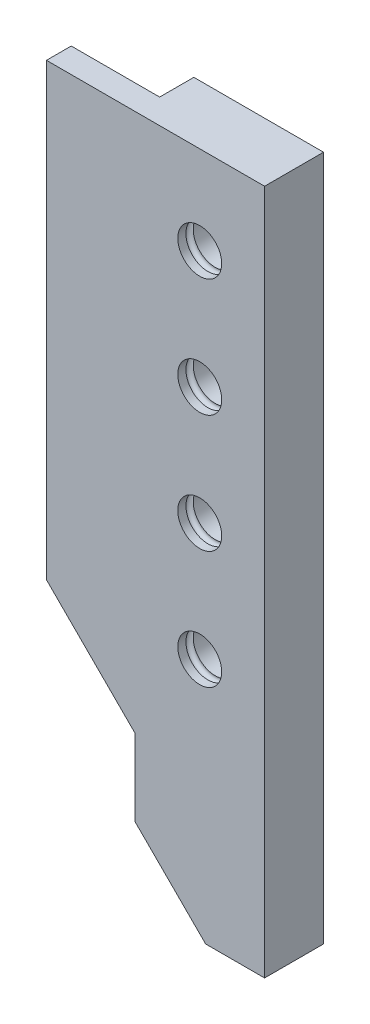
SolidWorks part; units mm, degrees
ref_plane "Front Plane" through (0, 0, 0) normal (0, 0, 1) x (1, 0, 0)
ref_plane "Top Plane" through (0, 0, 0) normal (0, 1, 0) x (1, 0, 0)
ref_plane "Right Plane" through (0, 0, 0) normal (1, 0, 0) x (0, 0, -1)
sketch "Sketch1" plane through (0, 0, 0) normal (0, 0, 1) x (1, 0, 0)
  line L0 (25.2, 31.3209) -> (25.2, -45)
  line L1 (25.2, -45) -> (40.2, -60)
  line L2 (40.2, -60) -> (40.2, 0) construction
  line L3 (40.2, -60) -> (40.2, -85)
  line L5 (62.2, -85) -> (62.2, 31.3209)
  line L6 (62.2, 31.3209) -> (25.2, 31.3209)
  line L12 (40.2, -85) -> (62.2, -85)
  line L13 (40.2, -60) -> (40.2, 31.3209)
  circle A0 centre (0, 0) radius 40.2 construction
  dimension "D1" = 80.4
  dimension "D2" = 15
  dimension "D3" = 15
  dimension "D4" = 60
  dimension "D5" = 25
  dimension "D6" = 22
extrude "Boss-Extrude1" add sketch "Sketch1" along normal blind 4.2 contours L1 L13 L6 L0 | L13 L3 L12 L5 L6 region at (32.9237, -10.7014, 0) region at (51.2, -26.8395, 0)
extrude "Boss-Extrude2" add sketch "Sketch1<3>" against normal blind 5.8 contours L13 L3 L12 L5 L6 region at (51.2, -26.8395, 0)
sketch "Sketch1<3>" plane through (0, 0, 0) normal (0, 0, 1) x (1, 0, 0) same geometry as "Sketch1"
sketch "Sketch2" plane through (0, 0, 4.2) normal (0, 0, 1) x (1, 0, 0)
  line L1 (40.2, -85) -> (62.2, -85) construction
  line L2 (62.2, 31.3209) -> (25.2, 31.3209) construction
  circle A0 centre (51.2, 16.3209) radius 3.725
  point P5 (51.2, -85)
  dimension "D1" = 7.45
  dimension "D2" = 15
extrude "Cut-Extrude1" cut sketch "Sketch2" against normal up to next
ref_axis "Axis1" through (51.2, 16.3209, -5.8) along (0, 0, 1)
ref_plane "Plane1" through (51.2, 0, 0) normal (-1, 0, 0) x (0, 0, 1)
sketch "Sketch3" plane through (51.2, 0, 0) normal (-1, 0, 0) x (0, 0, 1)
  line L0 (4.2, 31.3209) -> (4.2, -45) construction
  line L1 (-5.8, -85) -> (-5.8, 31.3209) construction
  circle A0 centre (-3.8, 20.2459) radius 0.65
  circle A1 centre (2.2, 20.2459) radius 0.65
  dimension "D1" = 1.3
  dimension "D3" = 2
  dimension "D4" = 2
  dimension "D2" = 0.2
revolve "Cut-Revolve1" cut sketch "Sketch3" angle 360 about axis through (51.2, 16.3209, -5.8) along (0, 0, 1)
pattern_linear "LPattern1" count 4 spacing 20 along (0, -1, 0) of "Cut-Extrude1", "Cut-Revolve1"
sketch "Sketch4" plane through (0, 0, 4.2) normal (0, 0, 1) x (1, 0, 0)
  line L0 (52.2, -85) -> (40.2, -73)
  line L1 (40.2, -85) -> (62.2, -85) construction
  line L2 (40.2, -85) -> (40.2, -60) construction
  line L3 (40.2, -73) -> (40.2, -85)
  line L4 (40.2, -85) -> (52.2, -85)
  dimension "D1" = 10
  dimension "D2" = 45
extrude "Cut-Extrude2" cut sketch "Sketch4" against normal up to next
ref_plane "Plane2" through (25.2, -45, 0) normal (0, -1, 0) x (-1, 0, 0)
sketch "Sketch6" plane through (25.2, 0, 0) normal (-1, 0, 0) x (0, 0, 1)
  line L0 (4.2, -45) -> (0, -45)
  line L1 (-20.9883, -45) -> (20.9883, -45) construction
  line L2 (4.2, -45) -> (4.2, -60) construction
  line L3 (0, -45) -> (3.7, -60)
  line L4 (4.2, -60) -> (0, -60) construction
  line L5 (3.7, -60) -> (4.2, -60)
  line L6 (4.2, -60) -> (4.2, -45)
  line L8 (4.2, -45) -> (0, -45)
  line L9 (4.2, -45) -> (4.2, -60)
  line L10 (4.2, -60) -> (0, -60)
  line L11 (0, -45) -> (0, -60)
  dimension "D1" = 0.5
extrude "Cut-Extrude3" cut sketch "Sketch6" against normal up to surface (15 mm away) contours L3 L11 L10 region at (25.2, -55, 1.2333) up to face at (40.2, -33.893, -0.5333)
